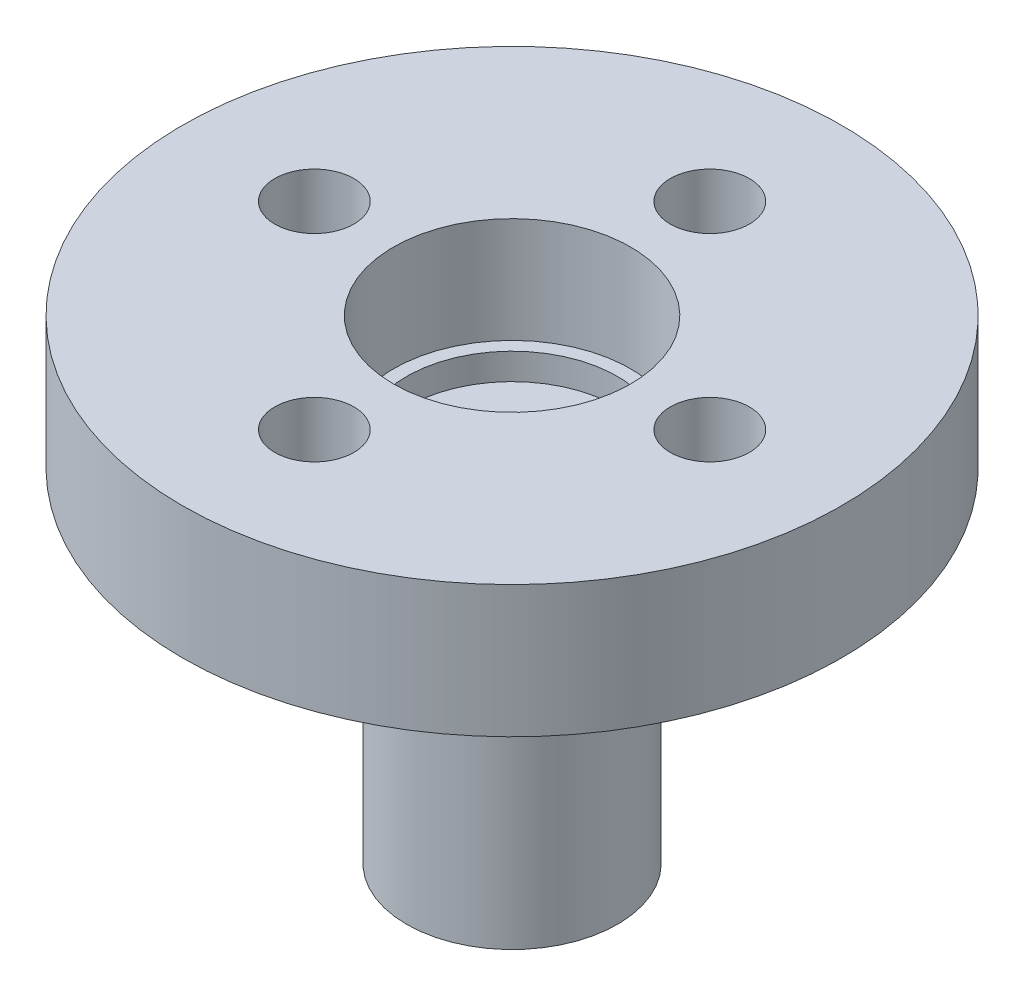
SolidWorks part; units mm, degrees
ref_plane "Front Plane" through (0, 0, 0) normal (0, 0, 1) x (1, 0, 0)
ref_plane "Top Plane" through (0, 0, 0) normal (0, 1, 0) x (1, 0, 0)
ref_plane "Right Plane" through (0, 0, 0) normal (1, 0, 0) x (0, 0, -1)
sketch "Sketch1" plane through (0, 0, 0) normal (0, 1, 0) x (1, 0, 0)
  circle A0 centre (0, 0) radius 7.5 construction
  circle A1 centre (0, 0) radius 4.5
  circle A2 centre (0, 7.5) radius 1.5
  circle A3 centre (7.5, 0) radius 1.5
  circle A4 centre (0, -7.5) radius 1.5
  circle A5 centre (-7.5, 0) radius 1.5
  circle A6 centre (0, 0) radius 12.5
  circle A7 centre (0, 0) radius 4
  point P15 (0, 0)
  dimension "D1" = 15
  dimension "D2" = 9
  dimension "D3" = 3
  dimension "D5" = 8
  dimension "D6" = 25
  dimension "D4" = 4
extrude "Boss-Extrude1" add sketch "Sketch1" along normal blind 5 contours A6 A1 A2 A3 A4 A5 region at (-12.1464, 0, 0)
extrude "Boss-Extrude2" add sketch "Sketch1<3>" against normal blind 13 separate body contours A7 region at (0, 0, 0)
sketch "Sketch1<3>" plane through (0, 0, 0) normal (0, 1, 0) x (1, 0, 0) same geometry as "Sketch1"
extrude "Boss-Extrude3" add sketch "Sketch1<4>" along normal blind 1 and the other way blind 1 contours A1 A7 region at (-4.3727, 0, 0)
sketch "Sketch1<4>" plane through (0, 0, 0) normal (0, 1, 0) x (1, 0, 0) same geometry as "Sketch1"
